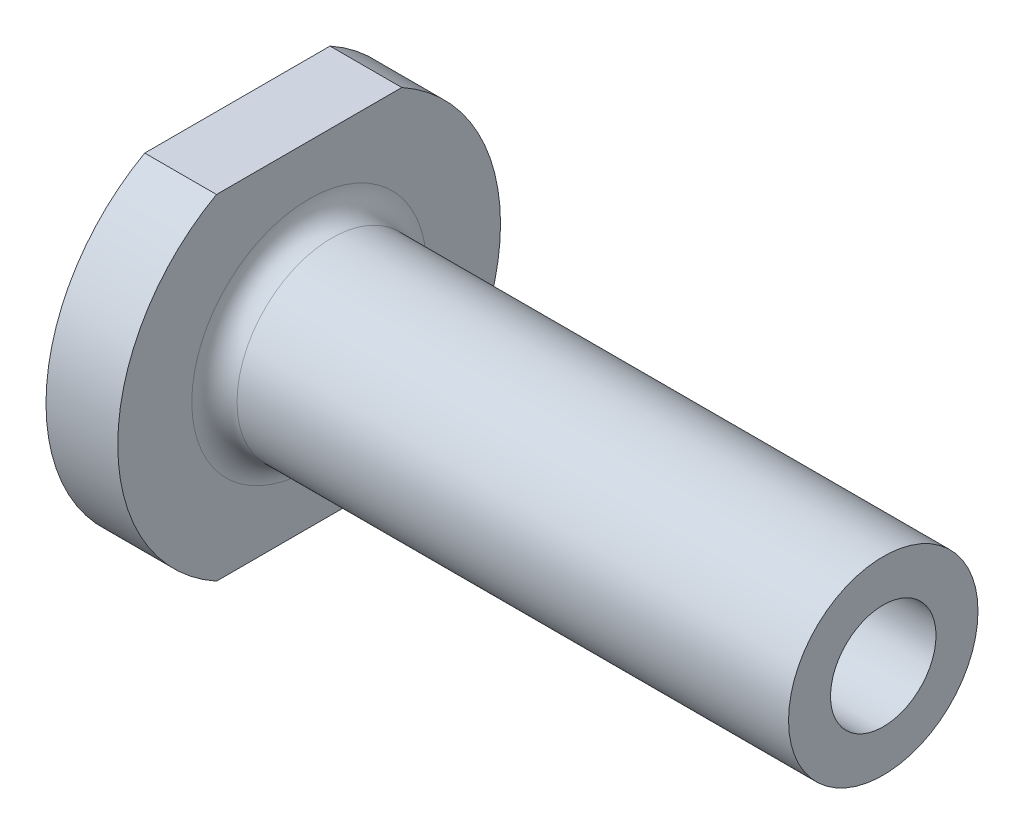
SolidWorks part; units mm, degrees
material "Alloy Steel"
ref_plane "Front Plane" through (0, 0, 0) normal (0, 0, 1) x (1, 0, 0)
ref_plane "Top Plane" through (0, 0, 0) normal (0, 1, 0) x (1, 0, 0)
ref_plane "Right Plane" through (0, 0, 0) normal (1, 0, 0) x (0, 0, -1)
sketch "Sketch1" plane through (0, 0, 0) normal (0, 0, 1) x (1, 0, 0)
  line L0 (0, 0) -> (-17.6508, 0) construction
  line L1 (0, 0) -> (42.8625, 0)
  line L2 (42.8625, 0) -> (42.8625, 6.2865)
  line L3 (42.8625, 6.2865) -> (4.7625, 6.2865)
  line L4 (4.7625, 6.2865) -> (4.7625, 12.7)
  line L5 (4.7625, 12.7) -> (0, 12.7)
  line L6 (0, 12.7) -> (0, 0)
  dimension "D1" = 12.573
  dimension "D2" = 42.8625
  dimension "D3" = 4.7625
  dimension "D4" = 25.4
revolve "Revolve1" add sketch "Sketch1" angle 360 about L0
fillet "Fillet1" radius 1.5 1 edges at (4.7625, 0, -6.2865)
hole_wizard "5/16-18" positions "Sketch2" profile "Sketch3" tap size "M8x1.0" standard "ANSI Metric" end condition through all
sketch "Sketch2" plane through (42.8625, 0, 0) normal (1, 0, 0) x (0, 0, -1)
  point P0 (0, 0)
sketch "Sketch3" plane through (42.8625, 0, 0) normal (0, 1, 0) x (0, 0, -1)
  line L0 (0, 0) -> (0, 42.8625)
  line L1 (0, 42.8625) -> (3.5, 42.8625)
  line L2 (3.5, 42.8625) -> (3.5, 0)
  line L5 (3.5, 0) -> (0, 0)
  line L11 (0, -6.35) -> (0, 107.95) construction
  dimension "Thru Tap Drill Dia." = 7
  dimension "Thru Tap Drill Depth" = 42.8625
cosmetic thread "Hole Thread1" parameters "D2"=8
sketch "Sketch4" plane through (0, 0, 0) normal (-1, 0, 0) x (0, 0, 1)
  line L0 (-6.1484, 11.1125) -> (6.1484, 11.1125)
  line L5 (6.1484, -11.1125) -> (-6.1484, -11.1125)
  arc A1 (6.1484, 11.1125) -> (-6.1484, 11.1125) centre (0, 0) ccw
  circle A2 centre (0, 0) radius 12.7
  arc A3 (-6.1484, -11.1125) -> (6.1484, -11.1125) centre (0, 0) ccw
  point P4 (0, 12.7)
  dimension "D1" = 0
  dimension "D2" = 1.5875
extrude "Cut-Extrude1" cut sketch "Sketch4" against normal through all
equation "\"D1@Sketch1\"=0.500000-.005"
